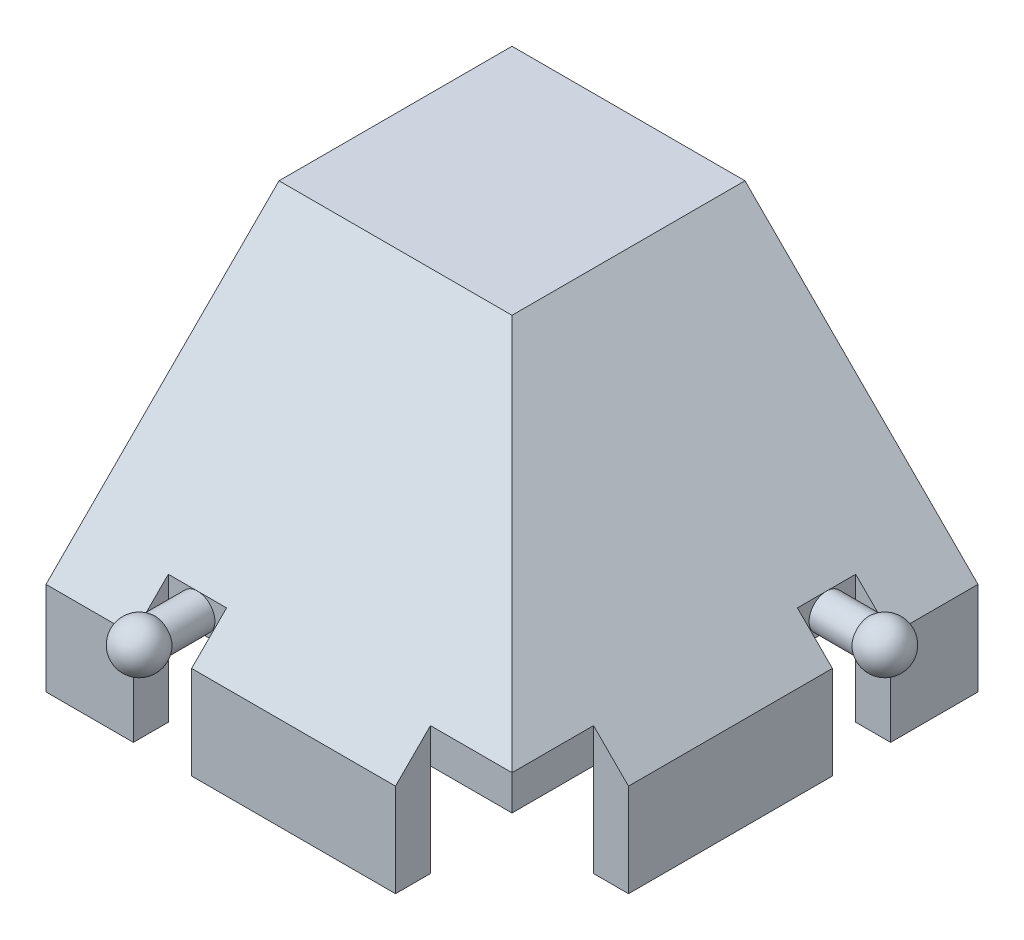
SolidWorks part; units mm, degrees
ref_plane "Front Plane" through (0, 0, 0) normal (0, 0, 1) x (1, 0, 0)
ref_plane "Top Plane" through (0, 0, 0) normal (0, 1, 0) x (1, 0, 0)
ref_plane "Right Plane" through (0, 0, 0) normal (1, 0, 0) x (0, 0, -1)
sketch "Sketch1" plane through (0, 0, 0) normal (0, 1, 0) x (1, 0, 0)
  line L1 (-21.6592, 15.8763) -> (18.3408, 15.8763)
  line L2 (-21.6592, 15.8763) -> (-21.6592, -24.1237)
  line L3 (-21.6592, -24.1237) -> (18.3408, -24.1237)
  line L4 (18.3408, 15.8763) -> (18.3408, -24.1237)
  dimension "D1" = 40
  dimension "D2" = 40
extrude "Boss-Extrude1" add sketch "Sketch1" along normal blind 20
chamfer "Chamfer1" distance 20 angle 45 2 edges at (18.3408, 20, 4.1237) (-1.6592, 20, 24.1237)
sketch "Sketch2" plane through (0, 0, 0) normal (0, -1, 0) x (1, 0, 0)
  line L0 (18.3408, 24.1237) -> (18.3408, -15.8763) construction
  line L1 (-21.6592, -15.8763) -> (15.3408, -15.8763)
  line L2 (-21.6592, -15.8763) -> (-21.6592, 21.1237)
  line L3 (-21.6592, 21.1237) -> (15.3408, 21.1237)
  line L4 (15.3408, -15.8763) -> (15.3408, 21.1237)
  line L5 (15.3408, -8.3763) -> (18.3408, -8.3763)
  line L6 (15.3408, -8.3763) -> (15.3408, -3.3763)
  line L7 (15.3408, -3.3763) -> (18.3408, -3.3763)
  line L8 (18.3408, -8.3763) -> (18.3408, -3.3763)
  line L9 (-21.6592, 24.1237) -> (18.3408, 24.1237) construction
  line L10 (-14.1592, 21.1237) -> (-9.1592, 21.1237)
  line L11 (-14.1592, 21.1237) -> (-14.1592, 24.1237)
  line L12 (-14.1592, 24.1237) -> (-9.1592, 24.1237)
  line L13 (-9.1592, 21.1237) -> (-9.1592, 24.1237)
  line L14 (8.3408, 24.1237) -> (8.3408, 21.1237)
  line L15 (15.3408, 14.1237) -> (18.3408, 14.1237)
  line M15 (18.3408, -15.8763) -> (18.3408, 24.1237)
  line M16 (18.3408, 24.1237) -> (-21.6592, 24.1237)
  dimension "D1" = 37
  dimension "D2" = 37
  dimension "D3" = 5
  dimension "D4" = 5
  dimension "D5" = 32.5
  dimension "D6" = 32.5
  dimension "D7" = 10
  dimension "D8" = 10
extrude "Cut-Extrude1" cut sketch "Sketch2" against normal blind 20 contours L4 L15 L14 L3 M15 M16 | L6 L5 L8 L7 | L11 L10 L13 L12 region at (15.4822, 0, 17.6237)
sketch "Sketch3" plane through (0, 0, 0) normal (0, -1, 0) x (1, 0, 0)
  line L0 (-14.1592, 21.1237) -> (-21.6592, 21.1237)
  line L1 (-21.6592, -15.8763) -> (-21.6592, 24.1237) construction
  line L2 (-9.1592, 21.1237) -> (8.3408, 21.1237)
  line L3 (15.3408, 14.1237) -> (15.3408, -3.3763)
  line L4 (15.3408, -8.3763) -> (15.3408, -15.8763)
  line L5 (18.3408, -15.8763) -> (-21.6592, -15.8763) construction
  line M2 (-14.1592, 21.1237) -> (-14.1592, 24.1237)
  line M3 (-14.1592, 24.1237) -> (-21.6592, 24.1237)
  line M4 (-21.6592, 24.1237) -> (-21.6592, -15.8763)
  line M5 (-21.6592, -15.8763) -> (18.3408, -15.8763)
  line M6 (18.3408, -15.8763) -> (18.3408, -8.3763)
  line M7 (18.3408, -8.3763) -> (15.3408, -8.3763)
  line M9 (15.3408, -3.3763) -> (18.3408, -3.3763)
  line M10 (18.3408, -3.3763) -> (18.3408, 14.1237)
  line M11 (18.3408, 14.1237) -> (15.3408, 14.1237)
  line M14 (8.3408, 21.1237) -> (8.3408, 24.1237)
  line M15 (8.3408, 24.1237) -> (-9.1592, 24.1237)
  line M16 (-9.1592, 24.1237) -> (-9.1592, 21.1237)
extrude "Boss-Extrude2" add sketch "Sketch3" along normal blind 8 contours L2 M16 M14 M15 | L3 M11 M9 M10 | L4 M7 M5 M6 | L0 M2 M3 M4 region at (16.8408, 0, -12.1263) region at (-17.9092, 0, 22.6237) region at (-0.4092, 0, 22.6237) region at (16.8408, 0, 5.3737)
sketch "Sketch4" plane through (0, 0, 21.1237) normal (0, 0, 1) x (1, 0, 0)
  line L0 (-9.1592, 3) -> (-14.1592, 3) construction
  circle A0 centre (-11.6592, 1.5) radius 1.5
  point P2 (0, 0)
  point P6 (0, 0)
  dimension "D1" = 3
  dimension "D2" = 1.5
  dimension "D3" = 2.5
extrude "Boss-Extrude3" add sketch "Sketch4" along normal blind 5 contours A0
sketch "Sketch5" plane through (0, 0, 26.1237) normal (0, 0, 1) x (1, 0, 0)
  line L0 (-11.6592, 3.5) -> (-11.6592, -0.5)
  arc A0 (-11.6592, 3.5) -> (-11.6592, -0.5) centre (-11.6592, 1.5) cw
  dimension "D1" = 2
revolve "Revolve1" add sketch "Sketch5" angle 360 about L0
sketch "Sketch6" plane through (15.3408, 0, 0) normal (1, 0, 0) x (0, 0, -1)
  line L0 (22, 0) -> (-22, 0) construction
  line L2 (3.3763, 0) -> (3.3763, 3) construction
  circle A0 centre (5.8763, 1.5) radius 1.5
  point P4 (0, 0)
  point P7 (0, 0)
  dimension "D1" = 3
  dimension "D2" = 1.5
  dimension "D3" = 2.5
extrude "Boss-Extrude4" add sketch "Sketch6" along normal blind 5
sketch "Sketch7" plane through (20.3408, 0, 0) normal (1, 0, 0) x (0, 0, -1)
  line L0 (5.8763, 3.5) -> (5.8763, -0.5)
  arc A0 (5.8763, 3.5) -> (5.8763, -0.5) centre (5.8763, 1.5) ccw
  dimension "D1" = 2
revolve "Revolve2" add sketch "Sketch7" angle 360 about L0
